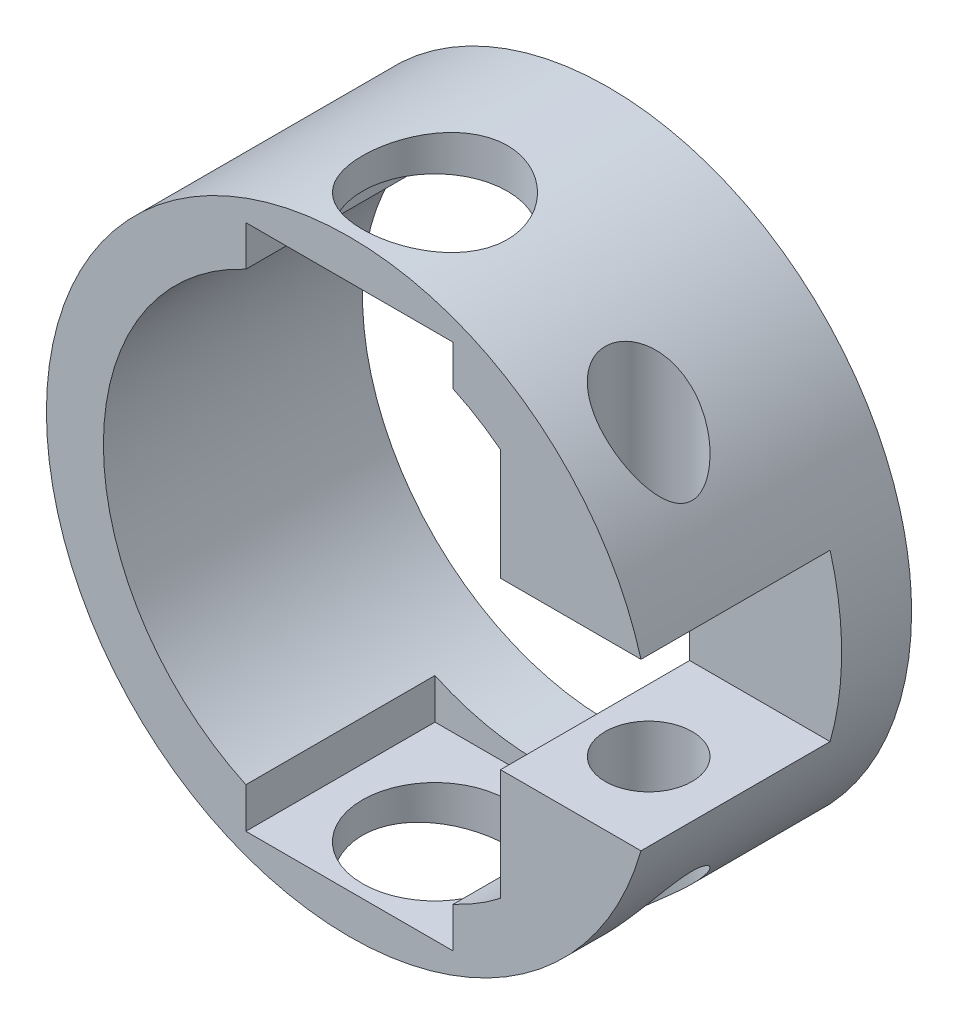
SolidWorks part; units mm, degrees
ref_plane "前视基准面" through (0, 0, 0) normal (0, 0, 1) x (1, 0, 0)
ref_plane "上视基准面" through (0, 0, 0) normal (0, 1, 0) x (1, 0, 0)
ref_plane "右视基准面" through (0, 0, 0) normal (1, 0, 0) x (0, 0, -1)
sketch "草图1" plane through (0, 0, 0) normal (0, 0, 1) x (1, 0, 0)
  line L0 (5.831, 7.5) -> (5.831, -7.5)
  circle A0 centre (0, 0) radius 11.7
  circle A1 centre (0, 0) radius 9.5 construction
  arc A2 (5.831, -7.5) -> (5.831, 7.5) centre (0, 0) cw
  dimension "D1" = 23.4
  dimension "D2" = 19
extrude "凸台-拉伸1" add sketch "草图1" along normal blind 10
sketch "草图2" plane through (0, 0, 0) normal (0, 1, 0) x (1, 0, 0)
  line L0 (0, 0) -> (0, -6.7) construction
  circle A0 centre (0, -6.7) radius 2.8
extrude "切除-拉伸1" cut sketch "草图2" against normal blind 20 and the other way blind 20
sketch "草图3" plane through (0, 0, 0) normal (0, 1, 0) x (1, 0, 0)
  line L0 (0, -6.7) -> (8.25, -6.7) construction
  circle A0 centre (8.25, -6.7) radius 1.675
extrude "切除-拉伸2" cut sketch "草图3" against normal blind 20 and the other way blind 20 contours A0
sketch "草图4" plane through (0, 0, 0) normal (0, 1, 0) x (1, 0, 0)
  line L1 (-4, -2.7) -> (4, -2.7)
  line L2 (-4, -2.7) -> (-4, -10.7)
  line L3 (-4, -10.7) -> (4, -10.7)
  line L4 (4, -2.7) -> (4, -10.7)
  line L5 (-4, -2.7) -> (4, -10.7) construction
  line L6 (-4, -10.7) -> (4, -2.7) construction
  point P0 (0, -6.7)
  dimension "D1" = 8
extrude "切除-拉伸3" cut sketch "草图4" against normal blind 10.175 and the other way blind 10.175
sketch "草图5" plane through (0, 0, 0) normal (0, 1, 0) x (1, 0, 0)
  line L1 (13.6213, -10.7) -> (2.8787, -10.7)
  line L2 (13.6213, -10.7) -> (13.6213, -2.7)
  line L3 (13.6213, -2.7) -> (2.8787, -2.7)
  line L4 (2.8787, -10.7) -> (2.8787, -2.7)
  line L5 (13.6213, -10.7) -> (2.8787, -2.7) construction
  line L6 (13.6213, -2.7) -> (2.8787, -10.7) construction
  point P0 (8.25, -6.7)
extrude "切除-拉伸4" cut sketch "草图5" against normal blind 3.2 and the other way blind 3.2
